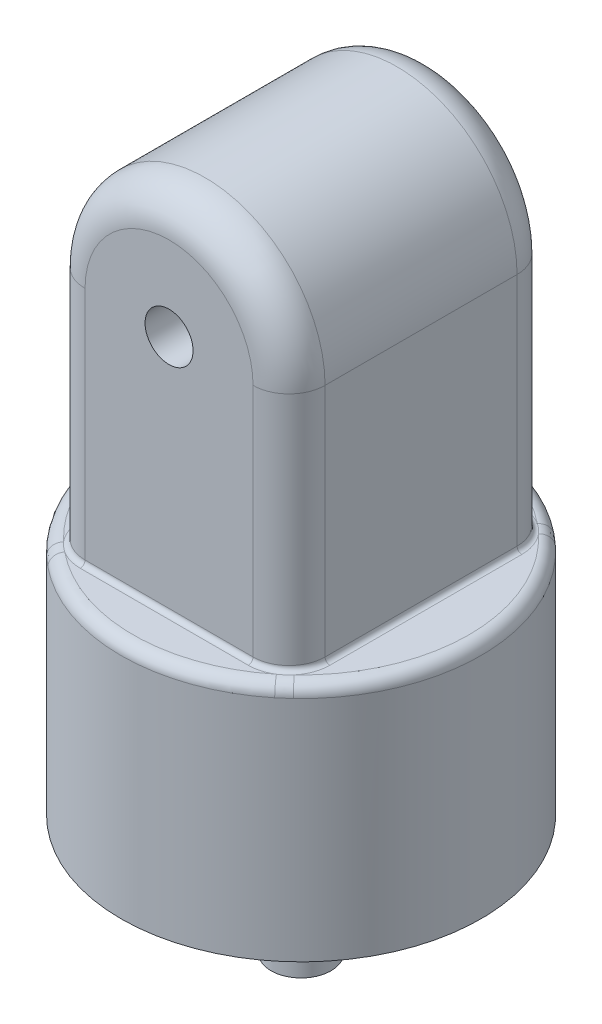
SolidWorks part; units mm, degrees
ref_plane "Front Plane" through (0, 0, 0) normal (0, 0, 1) x (1, 0, 0)
ref_plane "Top Plane" through (0, 0, 0) normal (0, 1, 0) x (1, 0, 0)
ref_plane "Right Plane" through (0, 0, 0) normal (1, 0, 0) x (0, 0, -1)
sketch "Sketch2" plane through (0, 0, 0) normal (0, 1, 0) x (1, 0, 0)
  circle A0 centre (0, 0) radius 75
  dimension "D1" = 150
extrude "Boss-Extrude1" add sketch "Sketch2" along normal blind 100
sketch "Sketch3" plane through (0, 0, 0) normal (0, -1, 0) x (1, 0, 0)
  circle A0 centre (0, 0) radius 12.5
  dimension "D1" = 25
extrude "Boss-Extrude2" add sketch "Sketch3" along normal blind 50
sketch "Sketch5" plane through (0, 100, 0) normal (0, 1, 0) x (1, 0, 0)
  line L1 (-50, 55) -> (50, 55)
  line L2 (-50, 55) -> (-50, -55)
  line L3 (-50, -55) -> (50, -55)
  line L4 (50, 55) -> (50, -55)
  line L5 (-50, 55) -> (50, -55) construction
  line L6 (-50, -55) -> (50, 55) construction
  point P0 (0, 0)
  point P8 (57.6544, 47.9684)
  point P9 (0, 0)
  dimension "D1" = 110
  dimension "D2" = 100
extrude "Boss-Extrude4" add sketch "Sketch5" along normal blind 150 contours L2 L1 L4 L3
fillet "Fillet2" 2 edges at (-50, 250, 0) (50, 250, 0) type full round first side face at (-50, 175, 0) second side face at (50, 175, 0) middle face at (0, 250, 0)
fillet "Fillet3" radius 15 6 edges at (-50, 150, 55) (0, 250, 55) (-50, 150, -55) (0, 250, -55) (50, 150, 55) (50, 150, -55)
fillet "Fillet4" radius 2 8 edges at (45.6066, 100, -50.6066) (0, 100, -55) (-45.6066, 100, -50.6066) (-50, 100, 0) (-45.6066, 100, 50.6066) (0, 100, 55) (45.6066, 100, 50.6066) (50, 100, 0)
fillet "Fillet5" radius 5 1 edges at (0, 100, 75)
sketch "Sketch6" plane through (0, 0, 55) normal (0, 0, 1) x (1, 0, 0)
  line L0 (0, 0) -> (0, 200) construction
  line L1 (0, 200) -> (35, 200) construction
  line L2 (35, 200) -> (0, 200) construction
  circle A0 centre (0, 200) radius 10
  dimension "D1" = 20
extrude "Cut-Extrude1" cut sketch "Sketch6" against normal up to surface (110 mm away) up to face at (0, 159.75, -55)
